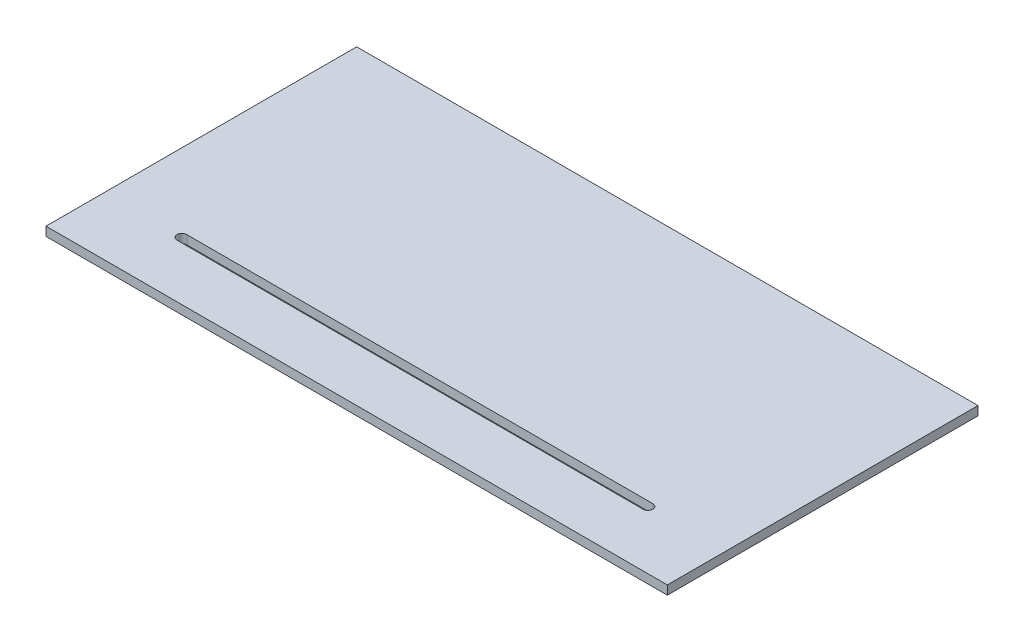
SolidWorks part; units mm, degrees
material "Cedar"
ref_plane "Front Plane" through (0, 0, 0) normal (0, 0, 1) x (1, 0, 0)
ref_plane "Top Plane" through (0, 0, 0) normal (0, 1, 0) x (1, 0, 0)
ref_plane "Right Plane" through (0, 0, 0) normal (1, 0, 0) x (0, 0, -1)
sketch "Sketch1" plane through (0, 0, 0) normal (0, 1, 0) x (1, 0, 0)
  line L1 (-609.6, -304.8) -> (609.6, -304.8)
  line L2 (-609.6, -304.8) -> (-609.6, 304.8)
  line L3 (-609.6, 304.8) -> (609.6, 304.8)
  line L4 (609.6, -304.8) -> (609.6, 304.8)
  line L5 (-609.6, -304.8) -> (609.6, 304.8) construction
  line L6 (-609.6, 304.8) -> (609.6, -304.8) construction
  point P0 (0, 0)
  dimension "D1" = 1219.2
  dimension "D2" = 609.6
extrude "Boss-Extrude1" add sketch "Sketch1" along normal blind 17.4752
sketch "Sketch2" plane through (0, 17.4752, 0) normal (0, 1, 0) x (1, 0, 0)
  line L0 (-457.2, -190.5) -> (457.2, -190.5) construction
  line L1 (-457.2, -180.975) -> (457.2, -180.975)
  line L2 (-457.2, -200.025) -> (457.2, -200.025)
  line L3 (0, -190.5) -> (0, 0) construction
  line L4 (-609.6, -304.8) -> (609.6, -304.8) construction
  arc A0 (-457.2, -180.975) -> (-457.2, -200.025) centre (-457.2, -190.5) ccw
  arc A1 (457.2, -200.025) -> (457.2, -180.975) centre (457.2, -190.5) ccw
  point P2 (0, -190.5)
  dimension "D1" = 19.05
  dimension "D2" = 914.4
  dimension "D3" = 114.3
extrude "Cut-Extrude1" cut sketch "Sketch2" against normal through all
